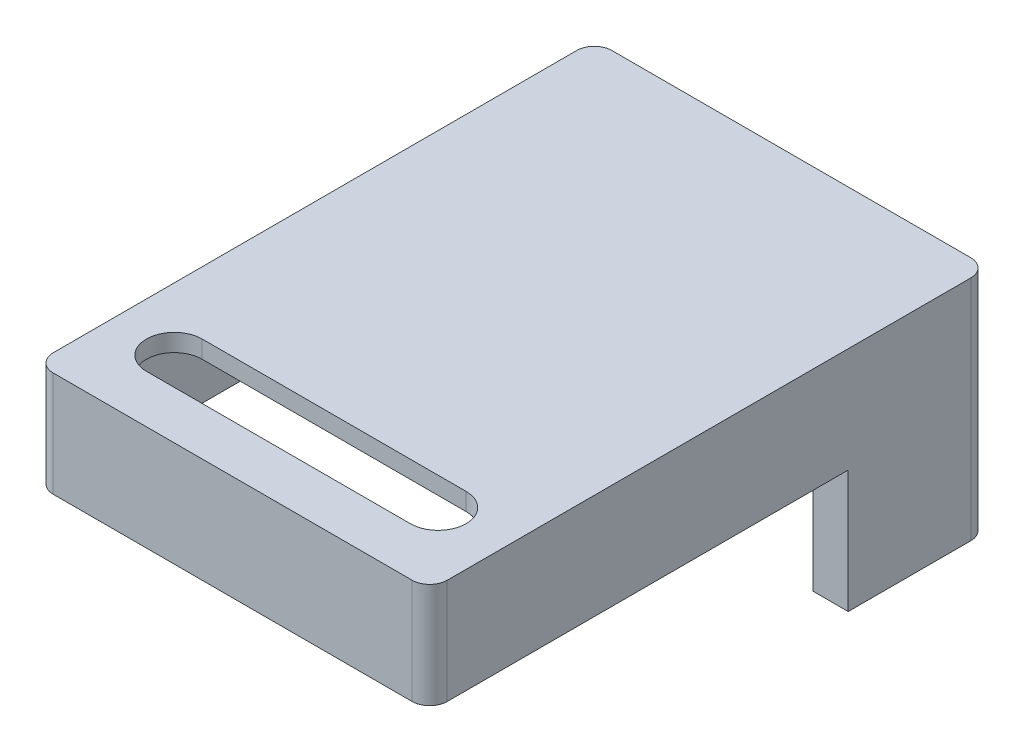
SolidWorks part; units mm, degrees
ref_plane "Front Plane" through (0, 0, 0) normal (0, 0, 1) x (1, 0, 0)
ref_plane "Top Plane" through (0, 0, 0) normal (0, 1, 0) x (1, 0, 0)
ref_plane "Right Plane" through (0, 0, 0) normal (1, 0, 0) x (0, 0, -1)
sketch "lid" plane through (0, 0, 0) normal (0, 1, 0) x (1, 0, 0)
  line L0 (9.25, 15) -> (10.5, 15)
  line L1 (-9.25, 15) -> (-10.5, 15)
  line L2 (-9.25, 21.75) -> (-9.25, 15)
  line L3 (-10, -8.15) -> (10, -8.15)
  line L4 (9.25, 21.75) -> (9.25, 15)
  line L5 (-8.75, 22.25) -> (8.75, 22.25)
  line L6 (10.5, 15) -> (11.25, 15)
  line L7 (10.5, 15) -> (10.5, -7.65)
  line L8 (-10.5, 15) -> (-11.25, 15)
  line L9 (-10.5, 15) -> (-10.5, -7.65)
  line L13 (-10.25, 23) -> (10.25, 23)
  line L14 (-11.25, 22) -> (-11.25, -7.9)
  line L15 (-10.25, -8.9) -> (10.25, -8.9)
  line L16 (11.25, 22) -> (11.25, -7.9)
  arc A0 (11.25, -7.9) -> (10.25, -8.9) centre (10.25, -7.9) cw
  arc A1 (-11.25, -7.9) -> (-10.25, -8.9) centre (-10.25, -7.9) ccw
  arc A2 (9.25, 21.75) -> (8.75, 22.25) centre (8.75, 21.75) ccw
  arc A3 (-8.75, 22.25) -> (-9.25, 21.75) centre (-8.75, 21.75) ccw
  arc A4 (-11.25, 22) -> (-10.25, 23) centre (-10.25, 22) cw
  arc A5 (10.25, 23) -> (11.25, 22) centre (10.25, 22) cw
  arc A6 (-10.5, -7.65) -> (-10, -8.15) centre (-10, -7.65) ccw
  arc A7 (10, -8.15) -> (10.5, -7.65) centre (10, -7.65) ccw
  point P0 (0, -8.9)
extrude "Boss-Extrude33" add sketch "lid" along normal blind 5 contours A0 A1 | A5 L2 A3 L5 A2 L4 region at (9.4888, 0, -18.375) region at (10.875, 0, -14.6718)
extrude "Boss-Extrude34" add sketch "lid<5>" along normal blind 1 from offset 5 contours L4 A2 L5 A3 L2 A0 | A0 A1 | A5 L2 A3 L5 A2 L4 region at (9.4888, 0, -18.375) region at (0, 0, -6.7117) region at (10.875, 0, -14.6718)
sketch "lid<5>" plane through (0, 0, 0) normal (0, 1, 0) x (1, 0, 0) same geometry as "lid"
extrude "Boss-Extrude35" add sketch "lid<6>" against normal blind 7 contours A5 L2 A3 L5 A2 L4 region at (9.4888, 0, -18.375)
sketch "lid<6>" plane through (0, 0, 0) normal (0, 1, 0) x (1, 0, 0) same geometry as "lid"
sketch "Sketch20" plane through (0, 6, 0) normal (0, 1, 0) x (1, 0, 0)
  line L0 (-7.6723, -4.5619) -> (7.3978, -4.5619) construction
  line L1 (-7.6723, -2.9667) -> (7.3978, -2.9667)
  line L2 (-7.6723, -6.1571) -> (7.3978, -6.1571)
  arc A0 (-7.6723, -2.9667) -> (-7.6723, -6.1571) centre (-7.6723, -4.5619) ccw
  arc A1 (7.3978, -6.1571) -> (7.3978, -2.9667) centre (7.3978, -4.5619) ccw
  point P2 (-0.1373, -4.5619)
extrude "Cut-Extrude2" cut sketch "Sketch20" against normal blind 2
